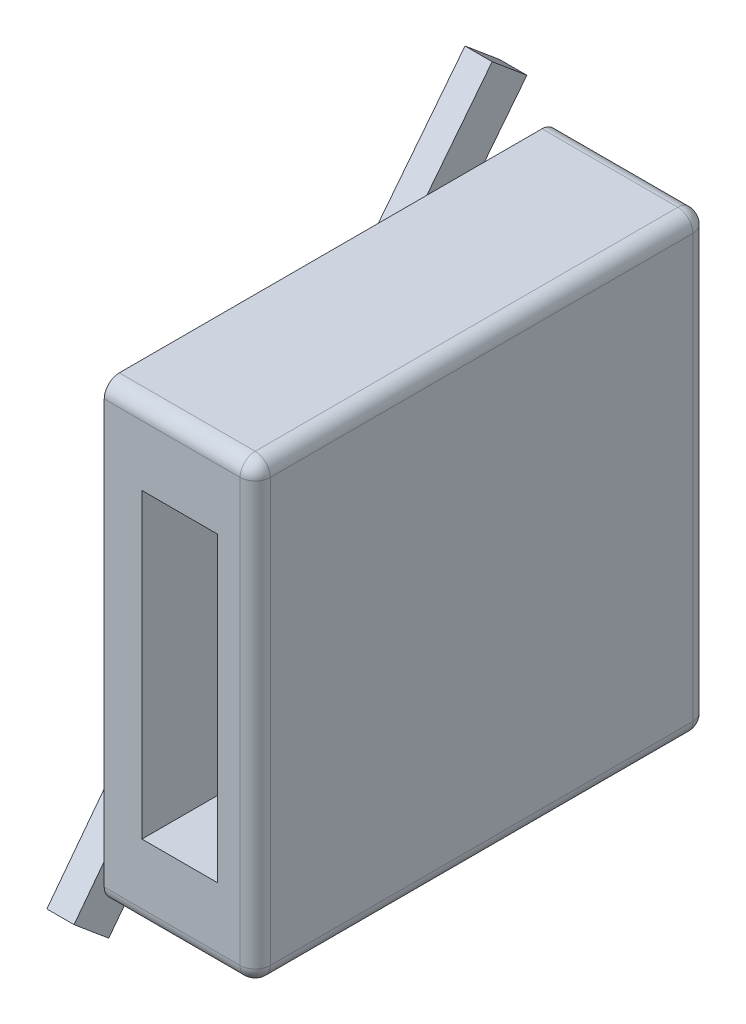
SolidWorks part; units mm, degrees
ref_plane "Спереди" through (0, 0, 0) normal (0, 0, 1) x (1, 0, 0)
ref_plane "Сверху" through (0, 0, 0) normal (0, 1, 0) x (1, 0, 0)
ref_plane "Справа" through (0, 0, 0) normal (1, 0, 0) x (0, 0, -1)
sketch "Эскиз2" plane through (0, 0, 0) normal (1, 0, 0) x (0, 0, -1)
  circle A0 centre (0, 0) radius 2
  dimension "D1" = 4
extrude "Бобышка-Вытянуть1" add sketch "Эскиз2" against normal blind 6 contours A0
ref_plane "Плоскость4" through (-2, 0, 0) normal (1, 0, 0) x (0, 0, -1)
sketch "Эскиз5" plane through (-2, 0, 0) normal (1, 0, 0) x (0, 0, -1)
  line L1 (-0.3004, 1.9773) -> (12.7002, 18.5)
  line L2 (1.9994, 0.0509) -> (15, 16.5736)
  line L3 (12.7002, 18.5) -> (15, 16.5736)
  line L4 (-4.9732, 0) -> (4.5633, 0) construction
  line L5 (0, 3.5493) -> (0, -3.8424) construction
  line L6 (-15, -17.1595) -> (-12.7002, -19.0859)
  line L9 (0.3004, -1.9773) -> (-12.7002, -19.0859)
  line L10 (-1.9994, -0.0509) -> (-15, -17.1595)
  arc A0 (-0.3004, 1.9773) -> (-1.9994, -0.0509) centre (0, 0) ccw
  arc A1 (0, -2) -> (1.9994, 0.0509) centre (0, 0) ccw
  dimension "D1" = 4
  dimension "D2" = 18.5
  dimension "D3" = 3
  dimension "D4" = 15
  dimension "D5" = 1.9773
  dimension "D6" = 1.9994
  dimension "D7" = 15
  dimension "D8" = 3
  dimension "D9" = 2
  dimension "D10" = 1.9773
  dimension "D12" = 0.0509
  dimension "D13" = 22.9252
extrude "Бобышка-Вытянуть2" add sketch "Эскиз5" against normal blind 1.8 contours L9 A1 L2 L3 L1 A0 L10 L6 region at (-2, -0.2286, 0.0722)
sketch "Эскиз6" plane through (0, 0, 0) normal (1, 0, 0) x (0, 0, -1)
  line L1 (15, -15) -> (-15, -15)
  line L2 (15, -15) -> (15, 15)
  line L3 (15, 15) -> (-15, 15)
  line L4 (-15, -15) -> (-15, 15)
  line L5 (15, -15) -> (-15, 15) construction
  line L6 (15, 15) -> (-15, -15) construction
  point P0 (0, 0)
  dimension "D1" = 30
extrude "Бобышка-Вытянуть3" add sketch "Эскиз6" along normal blind 10
sketch "Эскиз7" plane through (0, 0, 15) normal (0, 0, 1) x (1, 0, 0)
  line L1 (7.5, -10) -> (2.5, -10)
  line L2 (7.5, -10) -> (7.5, 10)
  line L3 (7.5, 10) -> (2.5, 10)
  line L4 (2.5, -10) -> (2.5, 10)
  line L5 (7.5, -10) -> (2.5, 10) construction
  line L6 (7.5, 10) -> (2.5, -10) construction
  point P0 (5, 0)
  dimension "D1" = 5
  dimension "D2" = 5
  dimension "D3" = 20
extrude "Вырез-Вытянуть1" cut sketch "Эскиз7" against normal through all
fillet "Скругление1" radius 1 8 edges at (5, 15, 15) (5, 15, -15) (10, -15, 0) (5, -15, -15) (5, -15, 15) (10, 0, -15) (10, 0, 15) (10, 15, 0)
